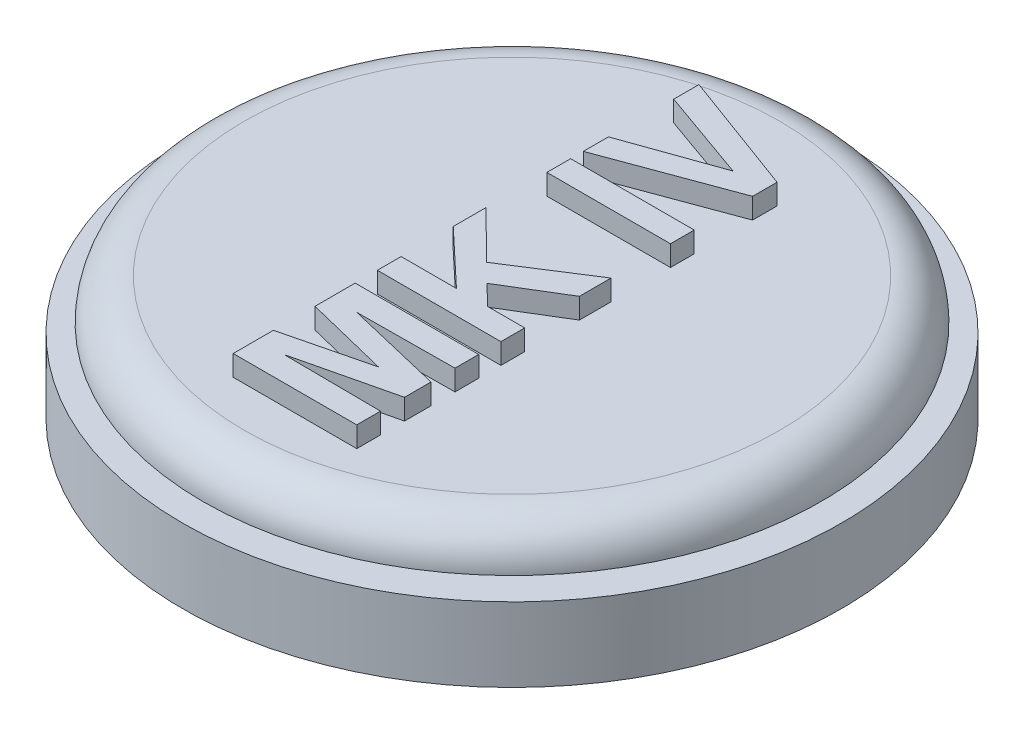
SolidWorks part; units mm, degrees
ref_plane "Спереди" through (0, 0, 0) normal (0, 0, 1) x (1, 0, 0)
ref_plane "Сверху" through (0, 0, 0) normal (0, 1, 0) x (1, 0, 0)
ref_plane "Справа" through (0, 0, 0) normal (1, 0, 0) x (0, 0, -1)
sketch "Sketch1" plane through (0, 0, 0) normal (0, 1, 0) x (1, 0, 0)
  circle A0 centre (0, 0) radius 12.3
  dimension "D1" = 24.6
extrude "Boss-Extrude1" add sketch "Sketch1" along normal blind 4
sketch "Sketch2" plane through (0, 4, 0) normal (0, 1, 0) x (1, 0, 0)
  circle A0 centre (0, 0) radius 15
  dimension "D1" = 30
extrude "Boss-Extrude2" add sketch "Sketch2" along normal blind 2
chamfer "Chamfer1" distance 0.5 angle 70 1 edges at (0, 0, 12.3) first distance on face at (0, 0, 12.3)
sketch "Sketch3" plane through (0, 6, 0) normal (0, 1, 0) x (1, 0, 0)
  line L0 (3.5, -14.586) -> (3.5, 14.586) construction
  line L1 (0, -15) -> (0, 15) construction
  circle A0 centre (0, 0) radius 15 construction
  text T0 "MK IV" font "Arial" height 6
  dimension "D1" = 3.5
extrude "Boss-Extrude3" add sketch "Sketch3" along normal blind 1
sketch "Sketch4" plane through (0, 0, 0) normal (0, -1, 0) x (1, 0, 0)
  circle A0 centre (0, 0) radius 12.8
  circle A1 centre (0, 0) radius 16
  circle A2 centre (0, 0) radius 11.8 construction
  circle A3 centre (0, 0) radius 15 construction
  dimension "D1" = 1
  dimension "D2" = 1
extrude "Boss-Extrude4" add sketch "Sketch4" against normal offset from surface (3.6 mm away) 0.4 separate body up to face at (0, 4, 12.3)
fillet "Fillet1" radius 2 1 edges at (0, 6, 15)
